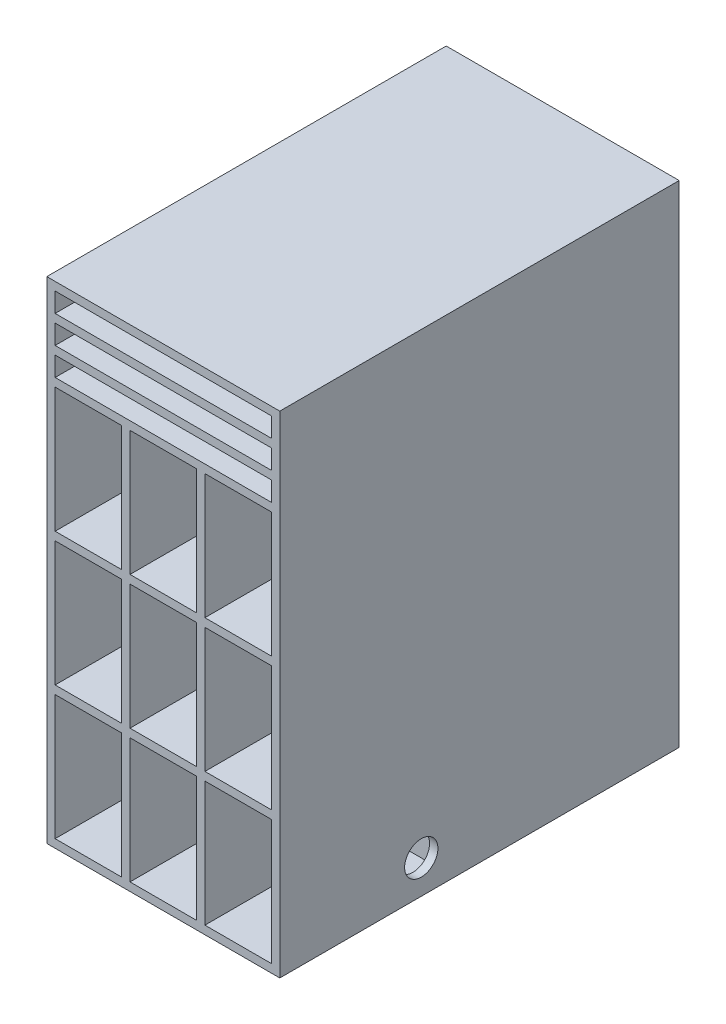
SolidWorks part; units mm, degrees
ref_plane "Front Plane" through (0, 0, 0) normal (0, 0, 1) x (1, 0, 0)
ref_plane "Top Plane" through (0, 0, 0) normal (0, 1, 0) x (1, 0, 0)
ref_plane "Right Plane" through (0, 0, 0) normal (1, 0, 0) x (0, 0, -1)
sketch "Sketch4" plane through (0, 0, 0) normal (0, 0, 1) x (1, 0, 0)
  line L1 (-177.8, -311.15) -> (177.8, -311.15)
  line L2 (-177.8, -311.15) -> (-177.8, 311.15)
  line L3 (-177.8, 311.15) -> (177.8, 311.15)
  line L4 (177.8, -311.15) -> (177.8, 311.15)
  line L5 (-177.8, -311.15) -> (177.8, 311.15) construction
  line L6 (-177.8, 311.15) -> (177.8, -311.15) construction
  point P0 (0, 0)
  dimension "D1" = 355.6
  dimension "D2" = 622.3
extrude "Boss-Extrude4" add sketch "Sketch4" along normal mid plane 190.5
shell "Shell1" thickness 12.7 removed face at (0, 0, 95.25)
sketch "Sketch5" plane through (0, 0, 95.25) normal (0, 0, 1) x (1, 0, 0)
  line L0 (-177.8, 304.8) -> (177.8, 304.8) construction
  line L1 (0, 101.6) -> (0, -101.6) construction
  line L2 (-177.8, 311.15) -> (-177.8, -311.15) construction
  line L3 (177.8, -311.15) -> (177.8, 311.15) construction
  line L6 (-177.8, -304.8) -> (177.8, -304.8) construction
  line L7 (-177.8, -311.15) -> (-177.8, -298.45) construction
  line L8 (-177.8, -311.15) -> (177.8, -311.15) construction
  line L9 (-165.1, -298.45) -> (165.1, -298.45) construction
  line L10 (-177.8, 298.45) -> (-177.8, 311.15) construction
  line L11 (165.1, 298.45) -> (-165.1, 298.45) construction
  line L12 (-171.45, -304.8) -> (-171.45, 304.8) construction
  line L13 (171.45, 304.8) -> (171.45, -304.8) construction
  line L14 (177.8, 0) -> (165.1, 0) construction
  line L15 (165.1, -298.45) -> (165.1, 298.45) construction
  line L16 (-165.1, 0) -> (-177.8, 0) construction
  line L17 (-165.1, 298.45) -> (-165.1, -298.45) construction
  line L18 (-57.15, 298.45) -> (-57.15, -298.45)
  line L19 (-165.1, -298.45) -> (165.1, -298.45) construction
  line L20 (57.15, 304.8) -> (57.15, -304.8)
  line L21 (-165.1, 101.6) -> (165.1, 101.6)
  line L22 (-165.1, -101.6) -> (165.1, -101.6)
  line L23 (-57.15, 0) -> (-171.45, 0) construction
  line L24 (-57.15, 0) -> (57.15, 0) construction
  line L25 (0, 304.8) -> (0, 101.6) construction
  point P11 (-177.8, -304.8)
  point P22 (-177.8, 304.8)
  point P30 (171.45, 0)
  point P34 (-171.45, 0)
  point P48 (0, 0)
  point P52 (0, 0)
rib "Rib1" sketch "Sketch5" sketch "Sketch5" thickness 12.7 extrusion direction normal to sketch draft on no parameters "D1"=12.7
sketch "Sketch8" plane through (0, 0, -95.25) normal (0, 0, -1) x (-1, 0, 0)
  line L4 (-177.8, -311.15) -> (177.8, -311.15)
  line L5 (177.8, -311.15) -> (177.8, 311.15)
  line L6 (177.8, 311.15) -> (-177.8, 311.15)
  line L7 (-177.8, 311.15) -> (-177.8, -311.15)
  line L8 (-177.8, -311.15) -> (177.8, -311.15)
  line L9 (177.8, -311.15) -> (177.8, 311.15)
  line L10 (177.8, 311.15) -> (-177.8, 311.15)
  line L11 (-177.8, 311.15) -> (-177.8, -311.15)
  dimension "D1" = 0
extrude "Boss-Extrude6" add sketch "Sketch8" along normal blind 76.2
shell "Shell4" thickness 12.7 removed face at (114.3, 298.45, 6.35)
sketch "Sketch9" plane through (0, 0, -171.45) normal (0, 0, -1) x (-1, 0, 0)
  line L0 (-177.8, 311.15) -> (-177.8, -311.15) construction
  line L3 (-165.1, 63.5) -> (165.1, 63.5)
  line L4 (-165.1, 63.5) -> (-165.1, -63.5)
  line L5 (-165.1, -63.5) -> (165.1, -63.5)
  line L6 (165.1, 63.5) -> (165.1, -63.5)
  line L8 (-165.1, -63.5) -> (165.1, 63.5) construction
  line L9 (-165.1, 63.5) -> (165.1, -63.5) construction
  point P10 (0, 0)
  dimension "D4" = 127
  dimension "D5" = 12.7
extrude "Cut-Extrude1" cut sketch "Sketch9" against normal blind 12.7
sketch "Sketch12" plane through (0, 0, -82.55) normal (0, 0, 1) x (1, 0, 0)
  line L2 (63.5, 241.3) -> (63.5, 165.1)
  line L4 (63.5, 298.45) -> (63.5, 107.95) construction
  arc A0 (63.5, 241.3) -> (63.5, 165.1) centre (63.5, 203.2) cw
  point P8 (63.5, 203.2)
  dimension "D1" = 38.1
extrude "Cut-Extrude3" cut sketch "Sketch12" against normal up to next
pattern_linear "LPattern1" count 3 spacing 114.3 along (-1, 0, 0) count 3 spacing 203.2 along (0, -1, 0) of "Cut-Extrude3"
sketch "Sketch16" plane through (177.8, 0, 0) normal (1, 0, 0) x (0, 0, -1)
  line L0 (171.45, 311.15) -> (171.45, -311.15) construction
  line L1 (-95.25, -311.15) -> (171.45, -311.15) construction
  circle A0 centre (120.65, -260.35) radius 25.4
  dimension "D3" = 50.8
  dimension "D1" = 50.8
  dimension "D2" = 50.8
extrude "Cut-Extrude5" cut sketch "Sketch16" against normal through all
sketch "Sketch6" plane through (0, 311.15, 0) normal (0, 1, 0) x (1, 0, 0)
  line L4 (-177.8, 171.45) -> (-177.8, -95.25)
  line L5 (-177.8, -95.25) -> (177.8, -95.25)
  line L6 (177.8, -95.25) -> (177.8, 171.45)
  line L7 (177.8, 171.45) -> (-177.8, 171.45)
  line L8 (-177.8, 171.45) -> (-177.8, -95.25)
  line L9 (-177.8, -95.25) -> (177.8, -95.25)
  line L10 (177.8, -95.25) -> (177.8, 171.45)
  line L12 (177.8, 171.45) -> (-177.8, 171.45)
  dimension "D1" = 0
extrude "Boss-Extrude5" add sketch "Sketch6" along normal blind 127
sketch "Sketch10" plane through (0, 0, 95.25) normal (0, 0, 1) x (1, 0, 0)
  line L0 (-177.8, 438.15) -> (177.8, 438.15) construction
  line L1 (-165.1, 425.45) -> (165.1, 425.45)
  line L2 (-165.1, 425.45) -> (-165.1, 311.15)
  line L3 (-165.1, 311.15) -> (165.1, 311.15)
  line L4 (165.1, 425.45) -> (165.1, 311.15)
  line L5 (-177.8, 438.15) -> (-177.8, -311.15) construction
  line L6 (177.8, -311.15) -> (177.8, 438.15) construction
  line L7 (165.1, 298.45) -> (63.5, 298.45) construction
  dimension "D1" = 12.7
  dimension "D2" = 12.7
  dimension "D3" = 12.7
  dimension "D4" = 12.7
extrude "Cut-Extrude2" cut sketch "Sketch10" against normal offset from surface (254 mm away) 12.7 up to face at (0, 0, -171.45)
sketch "Sketch13" plane through (0, 0, 95.25) normal (0, 0, 1) x (1, 0, 0)
  line L0 (-177.8, 431.8) -> (177.8, 431.8) construction
  line L1 (-177.8, 438.15) -> (-177.8, -311.15) construction
  line L2 (177.8, -311.15) -> (177.8, 438.15) construction
  line L3 (-177.8, 304.8) -> (177.8, 304.8) construction
  line L4 (-177.8, 298.45) -> (-177.8, 311.15) construction
  line L5 (-165.1, 311.15) -> (165.1, 311.15) construction
  line L6 (-63.5, 298.45) -> (-165.1, 298.45) construction
  line L7 (-177.8, 425.45) -> (-177.8, 438.15) construction
  line L8 (-177.8, 438.15) -> (177.8, 438.15) construction
  line L9 (165.1, 425.45) -> (-165.1, 425.45) construction
  line L10 (-165.1, 389.4667) -> (165.1, 389.4667)
  line L11 (-165.1, 425.45) -> (-165.1, 311.15) construction
  line L12 (165.1, 311.15) -> (165.1, 425.45) construction
  line L13 (-165.1, 347.1333) -> (165.1, 347.1333)
  line L14 (-165.1, 425.45) -> (-165.1, 311.15) construction
  line L15 (165.1, 311.15) -> (165.1, 425.45) construction
  line L16 (0, 431.8) -> (0, 389.4667) construction
  line L17 (0, 389.4667) -> (0, 347.1333) construction
  line L18 (0, 347.1333) -> (0, 304.8) construction
  point P11 (-177.8, 304.8)
  point P20 (-177.8, 431.8)
rib "Rib3" sketch "Sketch13" sketch "Sketch13" thickness 12.7 extrusion direction normal to sketch draft on no parameters "D1"=12.7
sketch "Sketch14" plane through (0, 395.8167, 0) normal (0, 1, 0) x (1, 0, 0)
  line L0 (-165.1, 158.75) -> (165.1, 158.75) construction
  line L1 (165.1, -95.25) -> (165.1, 158.75) construction
  circle A0 centre (139.7, 133.35) radius 19.05
  dimension "D3" = 38.1
  dimension "D1" = 25.4
  dimension "D2" = 25.4
extrude "Cut-Extrude4" cut sketch "Sketch14" against normal up to surface (97.3667 mm away) up to face at (0, 298.45, -127)
sketch "Sketch15" plane through (0, 0, -171.45) normal (0, 0, -1) x (-1, 0, 0)
  line L0 (165.1, -63.5) -> (165.1, 63.5) construction
  line L1 (-177.8, 438.15) -> (177.8, 438.15)
  line L2 (-177.8, 438.15) -> (-177.8, -311.15)
  line L3 (-177.8, -311.15) -> (177.8, -311.15)
  line L4 (177.8, 438.15) -> (177.8, -311.15)
  line L5 (-165.1, 425.45) -> (165.1, 425.45)
  line L6 (-165.1, 425.45) -> (-165.1, -298.45)
  line L7 (-165.1, -298.45) -> (165.1, -298.45)
  line L8 (165.1, 425.45) -> (165.1, -298.45)
  line L9 (-165.1, 298.45) -> (-165.1, -260.35) construction
  dimension "D1" = 12.7
  dimension "D2" = 12.7
extrude "Boss-Extrude7" add sketch "Sketch15" along normal blind 342.9
